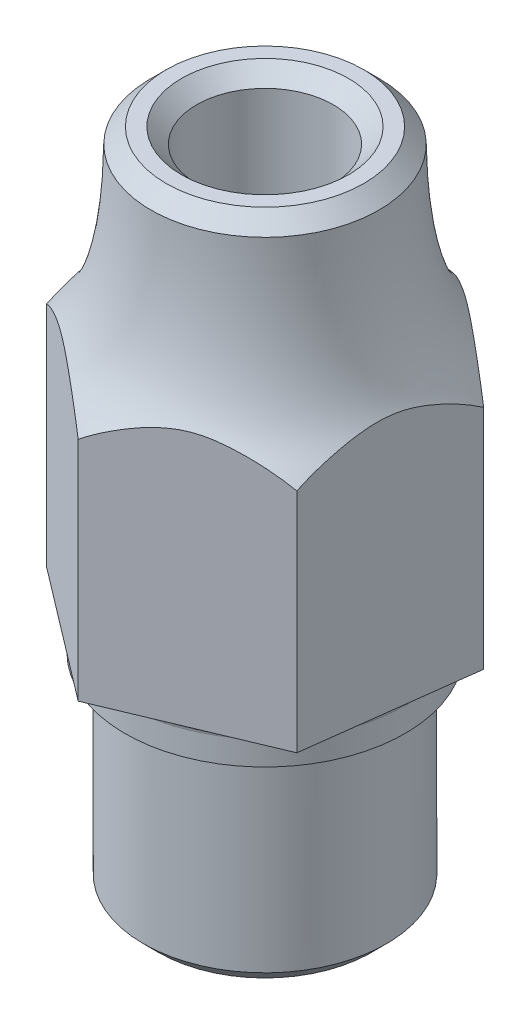
SolidWorks part; units mm, degrees
material "Acier allié inoxydable"
ref_plane "Plan de face" through (0, 0, 0) normal (0, 0, 1) x (1, 0, 0)
ref_plane "Plan de dessus" through (0, 0, 0) normal (0, 1, 0) x (1, 0, 0)
ref_plane "Plan de droite" through (0, 0, 0) normal (1, 0, 0) x (0, 0, -1)
sketch "Esquisse1" plane through (0, 0, 0) normal (0, 1, 0) x (1, 0, 0)
  circle A0 centre (0, 0) radius 4
  dimension "D1" = 8
extrude "Boss.-Extru.1" add sketch "Esquisse1" along normal blind 7.8
sketch "Esquisse2" plane through (0, 7.8, 0) normal (0, 1, 0) x (1, 0, 0)
  circle A0 centre (0, 0) radius 5.5
  dimension "D1" = 11
extrude "Boss.-Extru.2" add sketch "Esquisse2" along normal blind 14
sketch "Esquisse3" plane through (0, 21.8, 0) normal (0, 1, 0) x (1, 0, 0)
  line L1 (-0.6941, -5.456) -> (4.378, -3.3291)
  line L2 (4.378, -3.3291) -> (5.0721, 2.1269)
  line L3 (5.0721, 2.1269) -> (0.6941, 5.456)
  line L4 (0.6941, 5.456) -> (-4.378, 3.3291)
  line L5 (-4.378, 3.3291) -> (-5.0721, -2.1269)
  line L6 (-5.0721, -2.1269) -> (-0.6941, -5.456)
  circle A0 centre (0, 0) radius 4.7631 construction
extrude "Enlèv. mat.-Extru.1" cut sketch "Esquisse3" against normal blind 14 flip side to cut
sketch "Esquisse4" plane through (0, 0, 0) normal (0, 0, 1) x (1, 0, 0)
  line L0 (-0.6941, 21.8) -> (4.378, 21.8) construction
  line L2 (3.75, 19.4771) -> (3.75, 24.1229) construction
  line L3 (0, 0) -> (0, 21.8) construction
  line L4 (5.0721, 7.8) -> (5.0721, 21.8) construction
  line L5 (6.9079, 13.4166) -> (8.0378, 13.4166)
  line L6 (8.0378, 13.4166) -> (8.0378, 21.8)
  line L7 (8.0378, 21.8) -> (3.75, 21.8)
  spline S0 degree 3 poles (3.75, 21.8) (3.75, 20.2592) (3.8667, 17.1839) (5.9831, 14.7468) (6.3409, 13.9401) (6.9079, 13.4166) knots 0 0 0 0 0.502926 0.602926 1 1 1 1
  dimension "D1" = 8.3834
  dimension "D2" = 3.75
  dimension "D3" = 6
revolve "Enlèvement de matière-Révolution1" cut sketch "Esquisse4" angle 360 about L3
sketch "Esquisse5" plane through (0, 21.8, 0) normal (0, 1, 0) x (1, 0, 0)
  circle A0 centre (0, 0) radius 2.25
  dimension "D1" = 4.5
extrude "Enlèv. mat.-Extru.2" cut sketch "Esquisse5" against normal blind 20
sketch "Esquisse6" plane through (0, 0, 0) normal (0, -1, 0) x (1, 0, 0)
  line L1 (-1.1828, 1.3032) -> (-1.72, -0.3727)
  line L2 (-1.72, -0.3727) -> (-0.5372, -1.6759)
  line L3 (-0.5372, -1.6759) -> (1.1828, -1.3032)
  line L4 (1.1828, -1.3032) -> (1.72, 0.3727)
  line L5 (1.72, 0.3727) -> (0.5372, 1.6759)
  line L6 (0.5372, 1.6759) -> (-1.1828, 1.3032)
  circle A0 centre (0, 0) radius 1.5241 construction
  dimension "D1" = 3.44
extrude "Enlèv. mat.-Extru.3" cut sketch "Esquisse6" against normal blind 20
sketch "Esquisse7" plane through (0, 7.8, 0) normal (0, -1, 0) x (1, 0, 0)
  circle A0 centre (0, 0) radius 4.6108
extrude "Boss.-Extru.3" add sketch "Esquisse7" along normal blind 1
chamfer "Chanfrein1" distance 0.5 angle 45 3 edges at (0, 0, 4) (0, 21.8, 2.25) (0, 21.8, -3.75)
fillet "Congé1" radius 0.2 1 edges at (0, 7.8, 4.6108)
